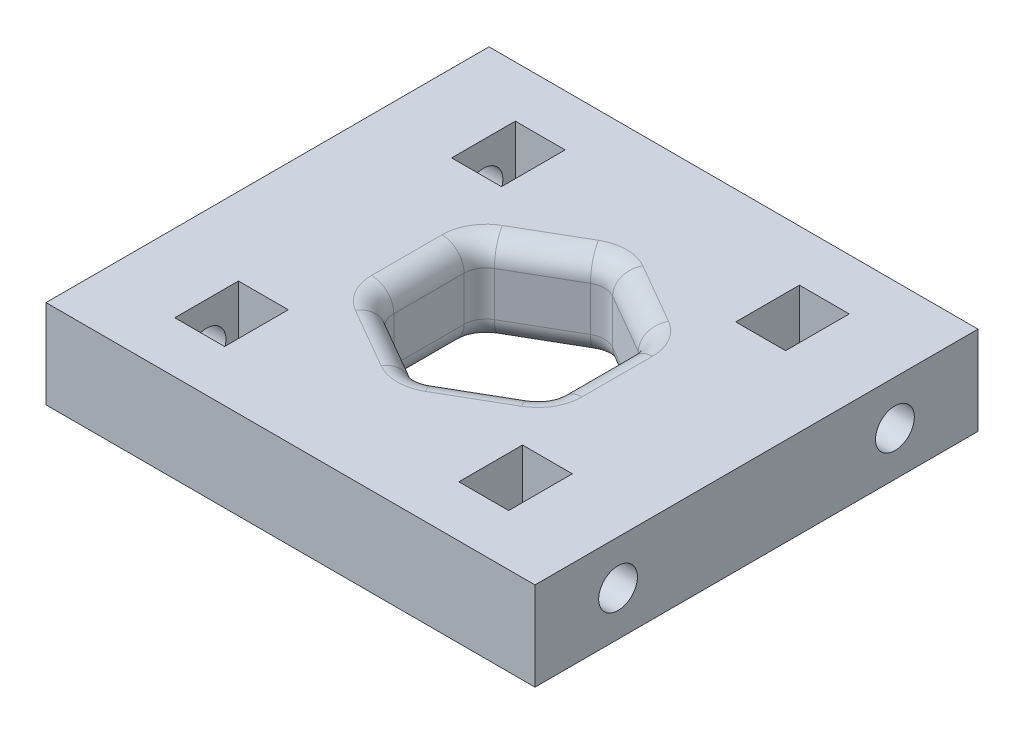
SolidWorks part; units mm, degrees
ref_plane "Front Plane" through (0, 0, 0) normal (0, 0, 1) x (1, 0, 0)
ref_plane "Top Plane" through (0, 0, 0) normal (0, 1, 0) x (1, 0, 0)
ref_plane "Right Plane" through (0, 0, 0) normal (1, 0, 0) x (0, 0, -1)
sketch "Sketch1" plane through (0, 0, 0) normal (1, 0, 0) x (0, 0, -1)
  line L1 (-20, 4) -> (20, 4)
  line L2 (-20, 4) -> (-20, -4)
  line L3 (-20, -4) -> (20, -4)
  line L4 (20, 4) -> (20, -4)
  line L5 (-20, 4) -> (20, -4) construction
  line L6 (-20, -4) -> (20, 4) construction
  point P0 (0, 0)
  dimension "D1" = 40
  dimension "D2" = 8
extrude "Boss-Extrude1" add sketch "Sketch1" along normal mid plane 44.15
sketch "Sketch2" plane through (22.075, 0, 0) normal (1, 0, 0) x (0, 0, -1)
  line L0 (0, 4) -> (0, -4) construction
  line L1 (20, 4) -> (-20, 4) construction
  line L2 (-20, -4) -> (20, -4) construction
  line L3 (-20, 0) -> (20, 0) construction
  line L4 (-20, 4) -> (-20, -4) construction
  line L5 (20, -4) -> (20, 4) construction
  circle A0 centre (-12.5, 0) radius 1.75
  circle A1 centre (12.5, 0) radius 1.75
  dimension "D2" = 3.5
  dimension "D1" = 25
extrude "Cut-Extrude1" cut sketch "Sketch2" against normal blind 7
ref_plane "Plane1" through (15.075, 0, 0) normal (1, 0, 0) x (0, 0, -1)
sketch "Sketch3" plane through (15.075, 0, 0) normal (1, 0, 0) x (0, 0, -1)
  line L0 (-15.375, 1.6599) -> (-15.375, 4)
  line L1 (-15.375, -1.6599) -> (-12.5, -3.3198)
  line L2 (-12.5, -3.3198) -> (-9.625, -1.6599)
  line L3 (-9.625, -1.6599) -> (-9.625, 1.6599)
  line L4 (-9.625, 1.6599) -> (-12.5, 3.3198)
  line L5 (-12.5, 3.3198) -> (-15.375, 1.6599)
  line L6 (-15.375, 1.6599) -> (-15.375, -1.6599)
  line L7 (20, 4) -> (-20, 4) construction
  line L8 (-15.375, 4) -> (-9.625, 4)
  line L9 (-9.625, 4) -> (-9.625, 1.6599)
  line L10 (0, 4) -> (0, -4) construction
  line L11 (-20, -4) -> (20, -4) construction
  line L12 (9.625, 4) -> (9.625, 1.6599)
  line L13 (15.375, 4) -> (9.625, 4)
  line L14 (15.375, 1.6599) -> (15.375, 4)
  line L15 (9.625, -1.6599) -> (9.625, 1.6599)
  line L16 (12.5, -3.3198) -> (9.625, -1.6599)
  line L17 (15.375, -1.6599) -> (12.5, -3.3198)
  line L18 (15.375, 1.6599) -> (15.375, -1.6599)
  circle A0 centre (-12.5, 0) radius 2.875 construction
  dimension "D1" = 5.75
extrude "Cut-Extrude2" cut sketch "Sketch3" against normal blind 4.5 contours L5 L6 L1 L2 L3 L4 | L9 L8 L0 L5 L4 | L18 L14 L13 L12 L15 L16 L17 region at (15.075, 2.8299, 15.3129) region at (15.075, 0, 12.5) region at (15.075, 0.7374, -12.5)
mirror "Mirror1" about plane through (0, 0, 0) normal (1, 0, 0) of "Cut-Extrude2", "Cut-Extrude1"
sketch "Sketch4" plane through (0, 4, 0) normal (0, 1, 0) x (1, 0, 0)
  line L1 (0, -8.6603) -> (7.5, -4.3301)
  line L2 (7.5, -4.3301) -> (7.5, 4.3301)
  line L3 (7.5, 4.3301) -> (0, 8.6603)
  line L4 (0, 8.6603) -> (-7.5, 4.3301)
  line L5 (-7.5, 4.3301) -> (-7.5, -4.3301)
  line L6 (-7.5, -4.3301) -> (0, -8.6603)
  circle A0 centre (0, 0) radius 7.5 construction
  dimension "D1" = 15
extrude "Cut-Extrude3" cut sketch "Sketch4" against normal up to next
fillet "Fillet1" radius 2 18 edges at (7.5, 4, 0) (7.5, -4, 0) (7.5, 0, 4.3301) (3.75, 4, 6.4952) (3.75, -4, 6.4952) (0, 0, 8.6603) (-3.75, 4, 6.4952) (-3.75, -4, 6.4952) (-7.5, 0, 4.3301) (-7.5, 4, 0) (-7.5, -4, 0) (-7.5, 0, -4.3301) (-3.75, 4, -6.4952) (-3.75, -4, -6.4952) (0, 0, -8.6603) (3.75, 4, -6.4952) (7.5, 0, -4.3301) (3.75, -4, -6.4952)
